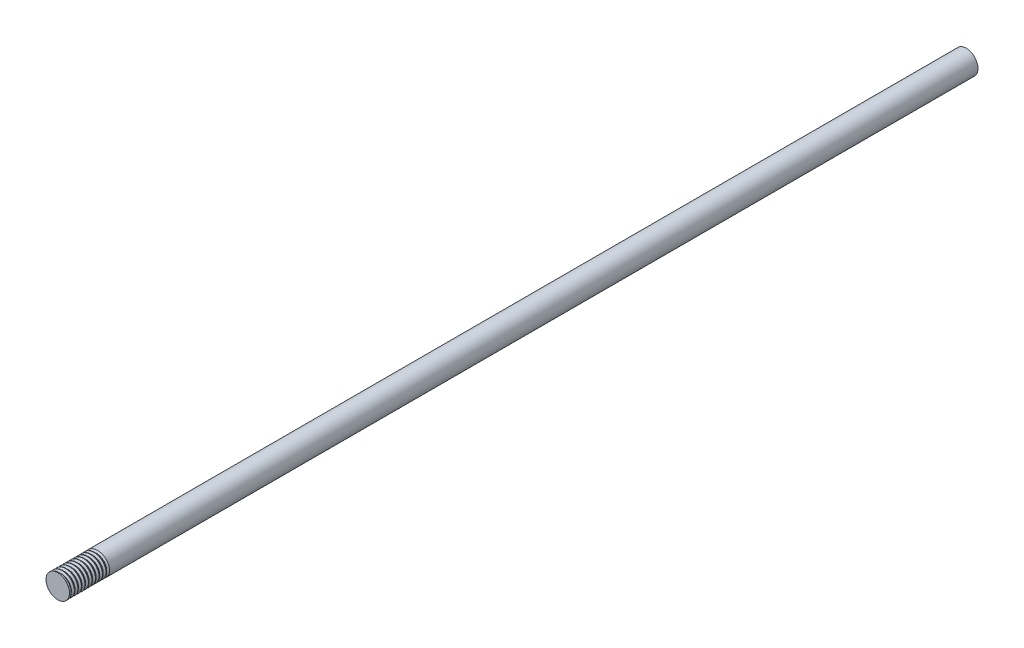
SolidWorks part; units mm, degrees
ref_plane "Alzado" through (0, 0, 0) normal (0, 0, 1) x (1, 0, 0)
ref_plane "Planta" through (0, 0, 0) normal (0, 1, 0) x (1, 0, 0)
ref_plane "Vista lateral" through (0, 0, 0) normal (1, 0, 0) x (0, 0, -1)
sketch "Croquis1" plane through (0, 0, 0) normal (0, 0, 1) x (1, 0, 0)
  circle A0 centre (0, 0) radius 1.5
  dimension "D1" = 3
extrude "Saliente-Extruir1" add sketch "Croquis1" along normal blind 116
cosmetic thread "Rosca cosmética1"
thread "Rosca1" pitch 0.45 method cut profile "Perfil de rosca1" start angle 0, offset 0, length 5, pitch 0.45, diameter 3
ref_plane "Plano1" through (-1.5, 0, 116) normal (0, -1, 0) x (-1, 0, 0)
sketch "Perfil de rosca1" plane through (-1.5, 0, 116) normal (0, -1, 0) x (-1, 0, 0)
  line L0 (0, 0) -> (0, 0.45) construction
  line L11 (0, 0) -> (0, 0.3937)
  line L12 (0, 0.3937) -> (-0.2436, 0.2531)
  line L13 (-0.2436, 0.2531) -> (-0.2436, 0.1406)
  line L15 (-0.2436, 0.1406) -> (0, 0)
  line L17 (-0.2436, 0.1969) -> (0, 0.1969) construction
  point P2 (0, 0)
  dimension "Pitch" = 0.45
  dimension "Profile_Angle" = 60
  dimension "Profile_Land" = 0.1125
  dimension "Profile_Height" = 0.2436
equation "\"D1@Saliente-Extruir1\"=240-22.5"
